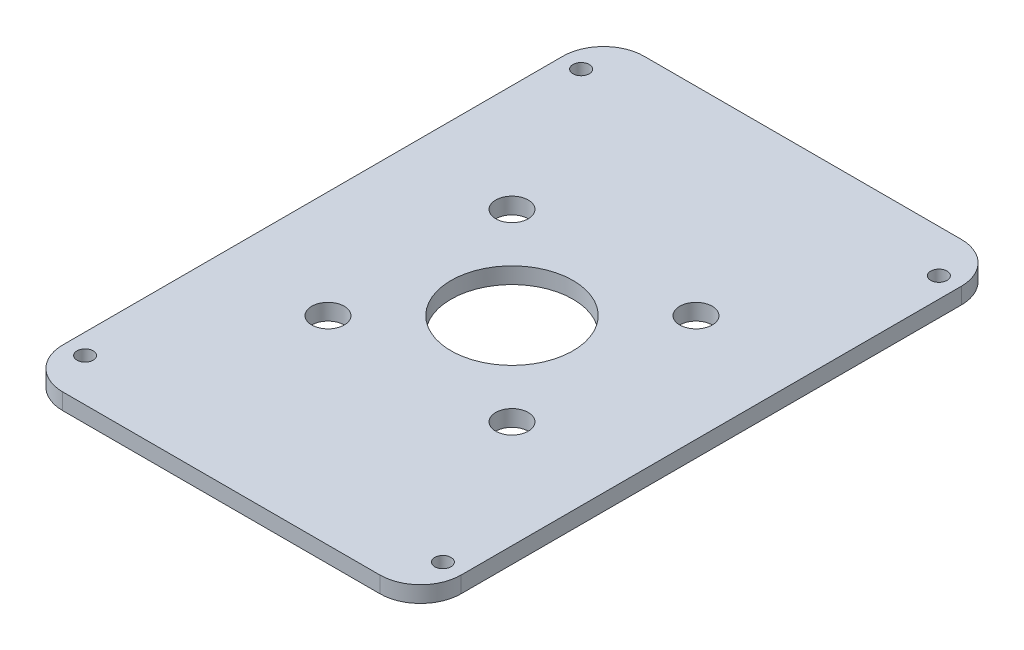
SolidWorks part; units mm, degrees
ref_plane "Front Plane" through (0, 0, 0) normal (0, 0, 1) x (1, 0, 0)
ref_plane "Top Plane" through (0, 0, 0) normal (0, 1, 0) x (1, 0, 0)
ref_plane "Right Plane" through (0, 0, 0) normal (1, 0, 0) x (0, 0, -1)
sketch "Sketch2" plane through (0, 0, 0) normal (0, 1, 0) x (1, 0, 0)
  line L0 (10.5954, 0) -> (0, 0) construction
  line L1 (-22, 30.5) -> (22, 30.5)
  line L2 (-22, 30.5) -> (-22, -30.5)
  line L3 (-22, -30.5) -> (22, -30.5)
  line L4 (22, 30.5) -> (22, -30.5)
  line L5 (-22, 30.5) -> (22, -30.5) construction
  line L6 (-22, -30.5) -> (22, 30.5) construction
  line L7 (-24.5, 35.75) -> (24.5, 35.75)
  line L8 (-24.5, 35.75) -> (-24.5, -35.75)
  line L9 (-24.5, -35.75) -> (24.5, -35.75)
  line L10 (24.5, 35.75) -> (24.5, -35.75)
  line L11 (-24.5, 35.75) -> (24.5, -35.75) construction
  line L12 (-24.5, -35.75) -> (24.5, 35.75) construction
  line L13 (0, 0) -> (0, 16.5808) construction
  line L14 (0, 0) -> (13.8408, 13.8408)
  circle A0 centre (-22, 30.5) radius 1
  circle A1 centre (22, 30.5) radius 1
  circle A2 centre (-22, -30.5) radius 1
  circle A3 centre (22, -30.5) radius 1
  circle A4 centre (0, 0) radius 7.5
  circle A6 centre (0, 0) radius 16
  circle A7 centre (11.3137, 11.3137) radius 2
  circle A8 centre (11.3137, -11.3137) radius 2
  circle A9 centre (-11.3137, -11.3137) radius 2
  circle A10 centre (-11.3137, 11.3137) radius 2
  point P0 (0, 0)
  point P7 (0, 0)
  point P32 (0, 0)
  dimension "D3" = 2
  dimension "D4" = 2
  dimension "D5" = 2
  dimension "D6" = 2
  dimension "D7" = 15
  dimension "D8" = 45
  dimension "D9" = 32
  dimension "D10" = 4
  dimension "D1" = 71.5
  dimension "D2" = 49
  dimension "D11" = 4
extrude "Boss-Extrude1" add sketch "Sketch2" along normal blind 2 contours L8 L9 L10 L7
extrude "Cut-Extrude2" cut sketch "Sketch2<6>" along normal blind 10 contours A0 | A4 | A2 | A3 | A1 | A7 | A8 | A9 | A10
sketch "Sketch2<6>" plane through (0, 0, 0) normal (0, 1, 0) x (1, 0, 0) same geometry as "Sketch2"
fillet "Fillet1" radius 5 4 edges at (24.5, 1, -35.75) (-24.5, 1, -35.75) (-24.5, 1, 35.75) (24.5, 1, 35.75)
